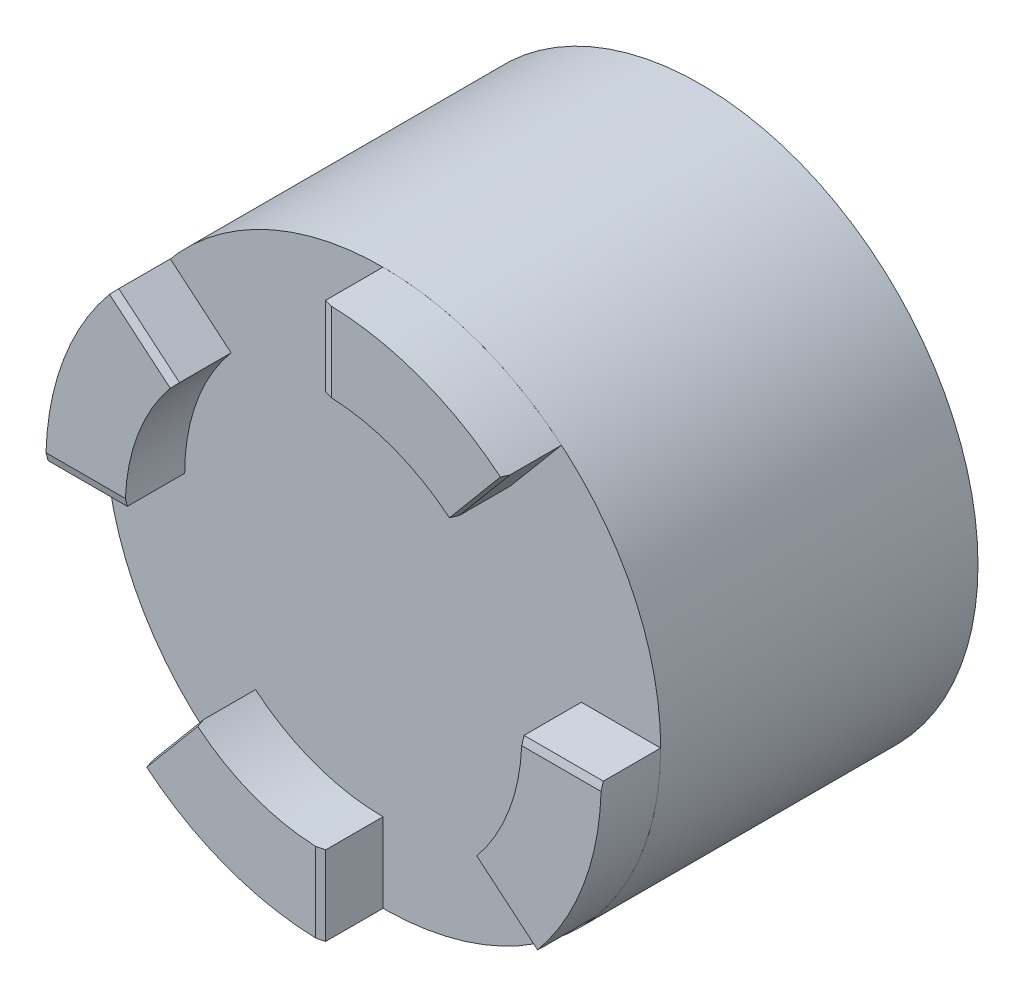
SolidWorks part; units mm, degrees
note: '?' marks a value the reader was unsure of.
ref_plane "Front Plane" through (0, 0, 0) normal (0, 0, 1) x (1, 0, 0)
ref_plane "Top Plane" through (0, 0, 0) normal (0, 1, 0) x (1, 0, 0)
ref_plane "Right Plane" through (0, 0, 0) normal (1, 0, 0) x (0, 0, -1)
sketch "Sketch1" plane through (0, 0, 0) normal (0, 0, 1) x (1, 0, 0)
  circle A0 centre (0, 0) radius 7
  dimension "D1" = 14
extrude "Boss-Extrude1" add sketch "Sketch1" along normal blind 8
sketch "Sketch2" plane through (0, 0, 8) normal (0, 0, 1) x (1, 0, 0)
  line L0 (0, 5) -> (0, 7)
  line L1 (3.2139, 3.8302) -> (4.4995, 5.3623)
  line L2 (0.6959, 4.9513) -> (0.9742, 6.9319)
  arc A0 (0, 7) -> (4.4995, 5.3623) centre (0, 0) cw
  circle A1 centre (0, 0) radius 7 construction
  arc A2 (0, 5) -> (3.2139, 3.8302) centre (0, 0) cw
  circle M5 centre (0, 0) radius 7
  dimension "D1" = 5
  dimension "D3" = 8
  dimension "D2" = 40
extrude "Boss-Extrude2" add sketch "Sketch2" along normal blind 1.5 separate body contours L0 A2 L2 M5 | L2 A2 L1 M5
ref_axis "Axis1" through (0, 0, 12) along (0, 0, -1)?
ref_plane "Plane1" through (0, 7, 0) normal (0, 1, 0) x (1, 0, 0)
sketch "Sketch10" plane through (0, 7, 0) normal (0, 1, 0) x (1, 0, 0)
  line L0 (0, -8) -> (4.4995, -8)
  line L1 (4.4995, -8) -> (4.4995, -9.5)
  line L2 (4.4995, -9.5) -> (3.2139, -9.5)
  line L3 (0, -8.7) -> (0, -8)
  line L4 (0, -8.7) -> (3.2139, -9.5)
  line L5 (4.4995, -8) -> (0, -8) construction
  dimension "D1" = 0.8
wrap "Wrap1" [suppressed] sketch "Sketch10" source sketch "Sketch10" thickness 3 parameters "D1"=3
chamfer "Chamfer2" distance 0.2 angle 15 2 edges at (3.8567, 4.5963, 9.5) (0, 6, 9.5)
fillet "Fillet1" [suppressed] radius 0.2
pattern_circular "CirPattern1" count 4 over 360 about axis through (0, 0, 0) along (0, 0, 1) of bodies 102
sketch "Sketch11" plane through (0, 0, 0) normal (0, 0, -1) x (-1, 0, 0)
  line L1 (2.05, -2.05) -> (-2.05, -2.05)
  line L2 (2.05, -2.05) -> (2.05, 2.05)
  line L3 (2.05, 2.05) -> (-2.05, 2.05)
  line L4 (-2.05, -2.05) -> (-2.05, 2.05)
  line L5 (2.05, -2.05) -> (-2.05, 2.05) construction
  line L6 (2.05, 2.05) -> (-2.05, -2.05) construction
  point P0 (0, 0)
  dimension "D1" = 4.1
extrude "Cut-Extrude1" cut sketch "Sketch11" against normal blind 6
fillet "Fillet2" radius 0.4 4 edges at (0, -2.05, 0) (-2.05, 0, 0) (0, 2.05, 0) (2.05, 0, 0)
